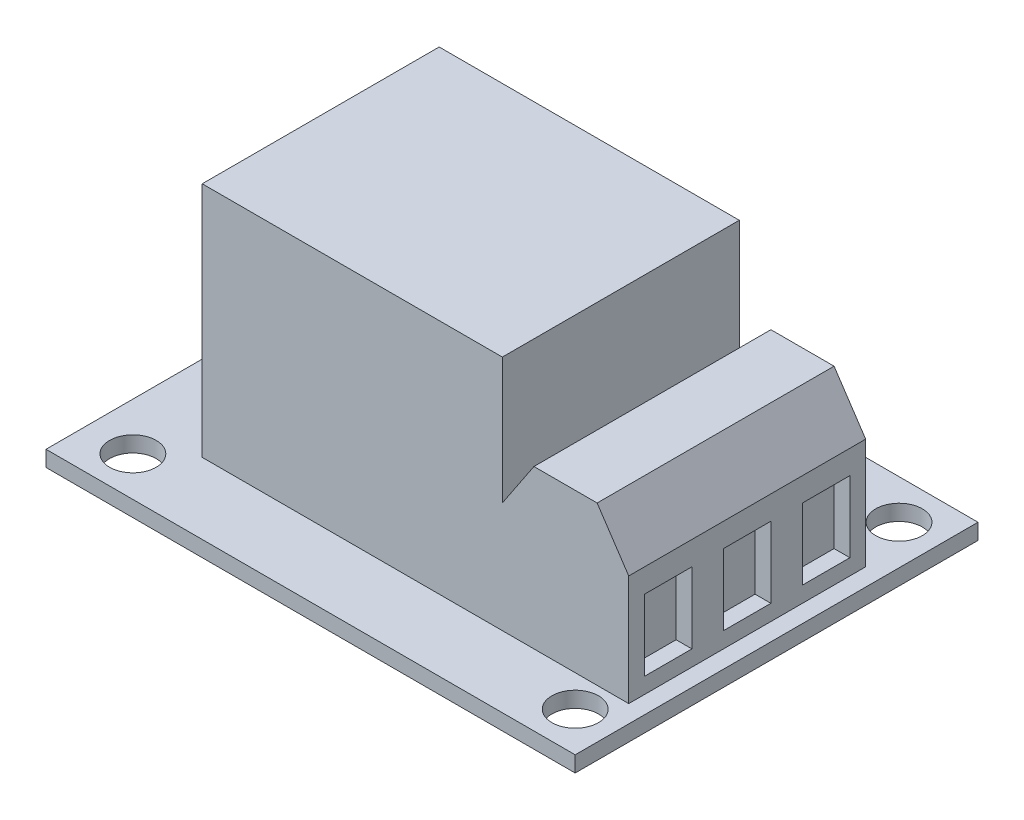
SolidWorks part; units mm, degrees
ref_plane "Plan de face" through (0, 0, 0) normal (0, 0, 1) x (1, 0, 0)
ref_plane "Plan de dessus" through (0, 0, 0) normal (0, 1, 0) x (1, 0, 0)
ref_plane "Plan de droite" through (0, 0, 0) normal (1, 0, 0) x (0, 0, -1)
sketch "Esquisse1" plane through (0, 0, 0) normal (0, 1, 0) x (1, 0, 0)
  line L0 (-19.137, 18.6513) -> (-19.137, -17.3618) construction
  line L1 (-22.137, 17.0607) -> (11.363, 17.0607)
  line L2 (-22.137, 17.0607) -> (-22.137, -8.4393)
  line L3 (-22.137, -8.4393) -> (11.363, -8.4393)
  line L4 (11.363, 17.0607) -> (11.363, -8.4393)
  line L5 (8.863, -17.3618) -> (8.863, 15.3259) construction
  line L6 (10.2525, 11.0607) -> (-16.7475, 11.0607)
  line L7 (10.2525, 11.0607) -> (10.2525, -3.9393)
  line L8 (10.2525, -3.9393) -> (-16.7475, -3.9393)
  line L9 (-16.7475, 11.0607) -> (-16.7475, -3.9393)
  line L10 (-44.4322, -5.9393) -> (49.6106, -5.9393) construction
  line L11 (44.7151, 14.5607) -> (-29.7816, 14.5607) construction
  line L12 (2.2525, -3.9393) -> (2.2525, 11.0607)
  circle A0 centre (-19.137, -5.9393) radius 1.475
  circle A1 centre (-19.137, 14.5607) radius 1.475
  circle A2 centre (8.863, -5.9393) radius 1.475
  circle A3 centre (8.863, 14.5607) radius 1.475
  dimension "D7" = 2.5
  dimension "D1" = 33.5
  dimension "D2" = 25.5
  dimension "D3" = 3
  dimension "D4" = 27
  dimension "D5" = 6
  dimension "D6" = 4.5
  dimension "D8" = 2.5
  dimension "D9" = 2.5
  dimension "D10" = 8
extrude "Boss.-Extru.9" add sketch "Esquisse1" against normal blind 1 contours L4 L1 L2 L3 A3 A2 A1 A0 L9 L6 L7 L8 | L8 L12 L6 L9 | L12 L8 L7 L6 region at (-5.387, 0, -16.6396) region at (6.2525, 0, -3.5607) region at (-7.2475, 0, -3.5607)
extrude "Boss.-Extru.12" add sketch "Esquisse1<17>" along normal blind 10 contours L12 L8 L7 L6 region at (6.2525, 0, -3.5607)
sketch "Esquisse1<17>" plane through (0, 0, 0) normal (0, 1, 0) x (1, 0, 0) same geometry as "Esquisse1"
chamfer "Chanfrein5" distance 2 distance2 3 2 edges at (2.2525, 10, -3.5607) (10.2525, 10, -3.5607) tangent propagation no first distance on face at (6.2525, 10, -3.5607)
sketch "Esquisse6" plane through (10.2525, 0, 0) normal (1, 0, 0) x (0, 0, -1)
  line L0 (2.0607, 5.5) -> (5.0607, 5.5)
  line L1 (2.0607, 5.5) -> (2.0607, 1)
  line L2 (5.0607, 5.5) -> (5.0607, 1)
  line L3 (2.0607, 1) -> (5.0607, 1)
  line L4 (7.0607, 5.5) -> (10.0607, 5.5)
  line L5 (7.0607, 5.5) -> (7.0607, 1)
  line L6 (10.0607, 5.5) -> (10.0607, 1)
  line L7 (-2.9393, 5.5) -> (0.0607, 5.5)
  line L8 (-2.9393, 5.5) -> (-2.9393, 1)
  line L9 (-2.9393, 1) -> (0.0607, 1)
  line L10 (0.0607, 5.5) -> (0.0607, 1)
  line L11 (7.0607, 1) -> (10.0607, 1)
  line L12 (-2.9393, 5.5) -> (2.0607, 5.5) construction
  dimension "D1" = 5
extrude "Enlèv. mat.-Extru.1" cut sketch "Esquisse6" against normal blind 1
extrude "Boss.-Extru.14" add sketch "Esquisse1<18>" along normal blind 15 contours L8 L12 L6 L9 region at (-7.2475, 0, -3.5607)
sketch "Esquisse1<18>" plane through (0, 0, 0) normal (0, 1, 0) x (1, 0, 0) same geometry as "Esquisse1"
